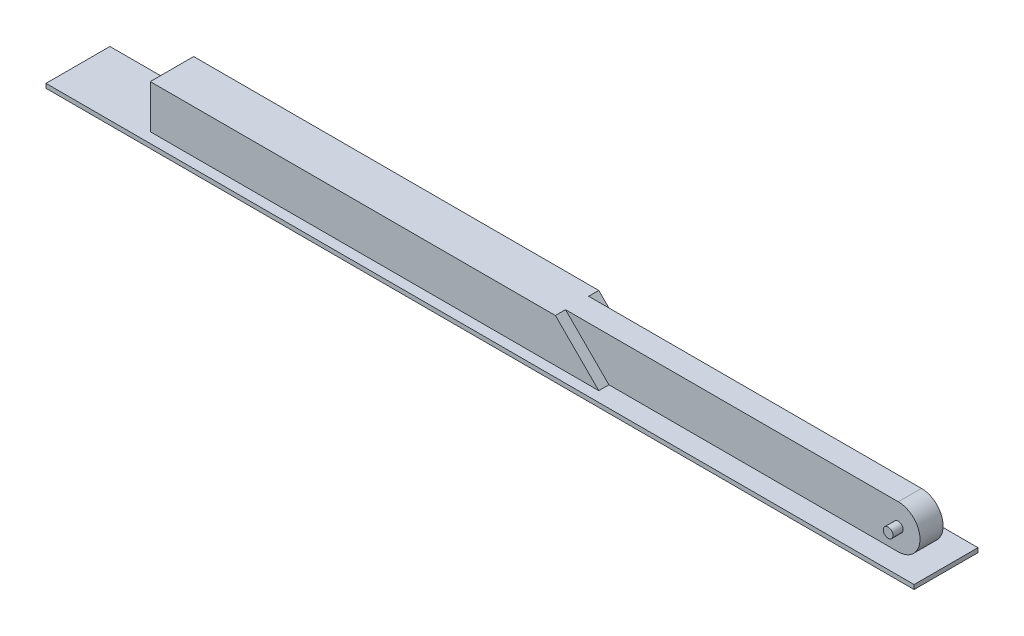
SolidWorks part; units mm, degrees
material "1060 Alloy"
ref_plane "Front Plane" through (0, 0, 0) normal (0, 0, 1) x (1, 0, 0)
ref_plane "Top Plane" through (0, 0, 0) normal (0, 1, 0) x (1, 0, 0)
ref_plane "Right Plane" through (0, 0, 0) normal (1, 0, 0) x (0, 0, -1)
sketch "Sketch1" plane through (0, 0, 0) normal (0, 0, 1) x (1, 0, 0)
  line L0 (-225, 0) -> (225, 0) construction
  line L1 (-225, 15) -> (225, 15)
  line L2 (-225, -15) -> (225, -15)
  arc A0 (-225, 15) -> (-225, -15) centre (-225, 0) ccw
  arc A1 (225, -15) -> (225, 15) centre (225, 0) ccw
  point P2 (0, 0)
  dimension "D1" = 450
  dimension "D2" = 30
extrude "Boss-Extrude1" add sketch "Sketch1" along normal mid plane 30
hole_wizard "H (0.266) Diameter Hole1" positions "Sketch2" profile "Sketch4" hole size "H" standard "ANSI Inch" end condition through all
sketch "Sketch2" plane through (0, 0, 15) normal (0, 0, 1) x (1, 0, 0)
  point P0 (-225, 0)
  point P3 (225, 0)
sketch "Sketch4" plane through (-225, 0, 15) normal (1, 0, 0) x (0, -1, 0)
  line L0 (0, 0) -> (0, 30)
  line L1 (0, 30) -> (3.3782, 30)
  line L2 (3.3782, 30) -> (3.3782, 0)
  line L5 (3.3782, 0) -> (0, 0)
  line L11 (0, -6.35) -> (0, 107.95) construction
  dimension "Thru Hole Dia." = 6.7564
  dimension "Thru Hole Depth" = 30
sketch "Sketch5" plane through (0, 15, 0) normal (0, 1, 0) x (1, 0, 0)
  line L1 (-257, 8) -> (-217, 8)
  line L2 (-257, 8) -> (-257, -8)
  line L3 (-257, -8) -> (-217, -8)
  line L4 (-217, 8) -> (-217, -8)
  line L5 (-217, 0) -> (0, 0) construction
  line L6 (-225, -15) -> (-225, 15) construction
  line L7 (225, -15) -> (225, 15) construction
  line L8 (25, 28.9161) -> (257, 28.9161)
  line L9 (25, 28.9161) -> (25, 8)
  line L10 (25, 8) -> (257, 8)
  line L11 (257, 28.9161) -> (257, 8)
  line L12 (25, -28.9161) -> (257, -28.9161)
  line L13 (25, -28.9161) -> (25, -8)
  line L14 (25, -8) -> (257, -8)
  line L15 (257, -28.9161) -> (257, -8)
  dimension "D1" = 16
  dimension "D2" = 8
  dimension "D3" = 40
  dimension "D4" = 200
  dimension "D5" = 32
extrude "Cut-Extrude1" cut sketch "Sketch5" against normal through all
sketch "Sketch6" plane through (0, 15, 0) normal (0, 1, 0) x (1, 0, 0)
  line L0 (25, 15) -> (25, 8) construction
  line L1 (-412.0368, 59.0418) -> (-175, 59.0418)
  line L2 (-412.0368, 59.0418) -> (-412.0368, -68.39)
  line L3 (-412.0368, -68.39) -> (-175, -68.39)
  line L4 (-175, 59.0418) -> (-175, -68.39)
  dimension "D1" = 200
extrude "Cut-Extrude2" cut sketch "Sketch6" against normal through all
sketch "Sketch10" plane through (-175, 0, 0) normal (-1, 0, 0) x (0, 0, 1)
  line L1 (15, -15) -> (-15, -15)
  line L2 (15, -15) -> (15, 15)
  line L3 (15, 15) -> (-15, 15)
  line L4 (-15, -15) -> (-15, 15)
  line L5 (15, -15) -> (-15, 15) construction
  line L6 (15, 15) -> (-15, -15) construction
  point P0 (0, 0)
extrude "Boss-Extrude3" add sketch "Sketch10" along normal blind 300
sketch "Sketch11" plane through (-475, 0, 0) normal (-1, 0, 0) x (0, 0, 1)
  line L0 (8, -15) -> (-8, -15) construction
  circle A0 centre (0, 3) radius 6.35
  dimension "D1" = 12.7
  dimension "D2" = 18
extrude "Cut-Extrude4" cut sketch "Sketch11" against normal blind 400
sketch "Sketch13" plane through (0, -15, 0) normal (0, -1, 0) x (-1, 0, 0)
  line L0 (386.2267, -22.0795) -> (386.2267, 22.0795) construction
  line L1 (349.98, -22.0795) -> (-250.02, -22.0795)
  line L2 (349.98, -22.0795) -> (349.98, 22.0795)
  line L3 (349.98, 22.0795) -> (-250.02, 22.0795)
  line L4 (-250.02, -22.0795) -> (-250.02, 22.0795)
  line L7 (-225, -8) -> (-225, 8) construction
  line L8 (-250.02, 0) -> (0, 0) construction
  point P0 (0, 0)
  dimension "D1" = 600
  dimension "D2" = 25.02
extrude "Boss-Extrude4" add sketch "Sketch13" along normal blind 3
sketch "Sketch14" plane through (0, 15, 0) normal (0, 1, 0) x (1, 0, 0)
  line L0 (225, -8) -> (225, 8) construction
  line L1 (-553.1047, 66.2219) -> (-285, 66.2219)
  line L2 (-553.1047, 66.2219) -> (-553.1047, -58.394)
  line L3 (-553.1047, -58.394) -> (-285, -58.394)
  line L4 (-285, 66.2219) -> (-285, -58.394)
  dimension "D1" = 510
  dimension "D2" = 268.1047
extrude "Cut-Extrude5" cut sketch "Sketch14" against normal up to surface (30 mm away) up to face at (-29.1567, -15, 0)
sketch "Sketch15" plane through (-285, 0, 0) normal (-1, 0, 0) x (0, 0, 1)
  line L1 (-6.35, -3.35) -> (6.35, -3.35)
  line L2 (-6.35, -3.35) -> (-6.35, 9.35)
  line L3 (-6.35, 9.35) -> (6.35, 9.35)
  line L4 (6.35, -3.35) -> (6.35, 9.35)
  line L5 (-6.35, -3.35) -> (6.35, 9.35) construction
  line L6 (-6.35, 9.35) -> (6.35, -3.35) construction
  point P0 (0, 3)
  dimension "D1" = 12.7
extrude "Cut-Extrude6" cut sketch "Sketch15" against normal blind 385
sketch "Sketch16" plane through (0, 0, 0) normal (0, 0, 1) x (1, 0, 0)
  circle A0 centre (225, 0) radius 3.3782
extrude "Boss-Extrude5" add sketch "Sketch16" along normal up to surface and the other way up to surface up to face at (-130, 0, 15) other way up to face at (-130, 0, -15)
chamfer "Chamfer1" distance 30 angle 45 2 edges at (25, 15, 11.5) (25, 15, -11.5)
